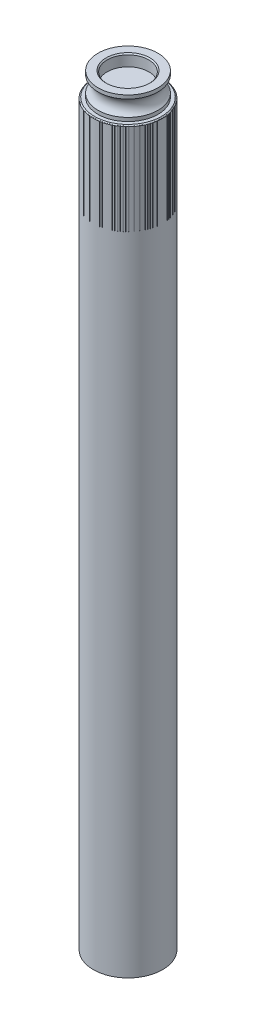
SolidWorks part; units mm, degrees
ref_plane "Front Plane" through (0, 0, 0) normal (0, 0, 1) x (1, 0, 0)
ref_plane "Top Plane" through (0, 0, 0) normal (0, 1, 0) x (1, 0, 0)
ref_plane "Right Plane" through (0, 0, 0) normal (1, 0, 0) x (0, 0, -1)
sketch "Sketch1" plane through (0, 0, 0) normal (0, 0, 1) x (1, 0, 0)
  line L0 (0, 0) -> (0, 330)
  line L5 (0, 330) -> (-13, 330)
  line L6 (-13, 330) -> (-13, 320)
  line L7 (-13, 320) -> (-15, 320)
  line L8 (-15, 320) -> (-15, 0)
  line L9 (-15, 0) -> (0, 0)
  dimension "D1" = 330
  dimension "D2" = 10
  dimension "D3" = 15
  dimension "D4" = 13
revolve "Revolve1" add sketch "Sketch1" angle 360 about L0
sketch "Sketch2" plane through (0, 0, 0) normal (0, 0, 1) x (1, 0, 0)
  line L0 (0, 0) -> (0, 330) construction
  line L2 (15, 320) -> (-15, 320) construction
  line L3 (-15.5, 325) -> (-13, 325) construction
  line L4 (-13, 330) -> (-13, 320) construction
  line L5 (13, 330) -> (-13, 330) construction
  line L6 (-13, 330) -> (-13, 320) construction
  circle A0 centre (-15.5, 325) radius 4.25
  dimension "D2" = 8.5
  dimension "D1" = 2.5
revolve "Cut-Revolve1" cut sketch "Sketch2" angle 360 about L0
sketch "Sketch3" plane through (0, 330, 0) normal (0, 1, 0) x (1, 0, 0)
  circle A3 centre (0, 0) radius 9
  circle A4 centre (0, 0) radius 9
  dimension "D1" = 4
extrude "Cut-Extrude1" cut sketch "Sketch3" against normal blind 5
chamfer "Chamfer1" distance 0.5 angle 45 2 edges at (0, 320, -15) (0, 330, 9)
sketch "Sketch4" plane through (0, 320, 0) normal (0, 1, 0) x (1, 0, 0)
  line L1 (-0.05, 14.8) -> (0.05, 14.8)
  line L2 (-0.05, 14.8) -> (-0.05, 15.2)
  line L3 (-0.05, 15.2) -> (0.05, 15.2)
  line L4 (0.05, 14.8) -> (0.05, 15.2)
  line L5 (-0.05, 14.8) -> (0.05, 15.2) construction
  line L6 (-0.05, 15.2) -> (0.05, 14.8) construction
  circle A0 centre (0, 0) radius 15 construction
  circle A1 centre (0, 0) radius 15 construction
  point P0 (0, 15)
  dimension "D1" = 0.1
  dimension "D2" = 0.4
extrude "Cut-Extrude2" cut sketch "Sketch4" against normal blind 40
pattern_circular "CirPattern1" count 110 over 360 about axis through (0, 330, 0) along (0, -1, 0) of "Cut-Extrude2"
